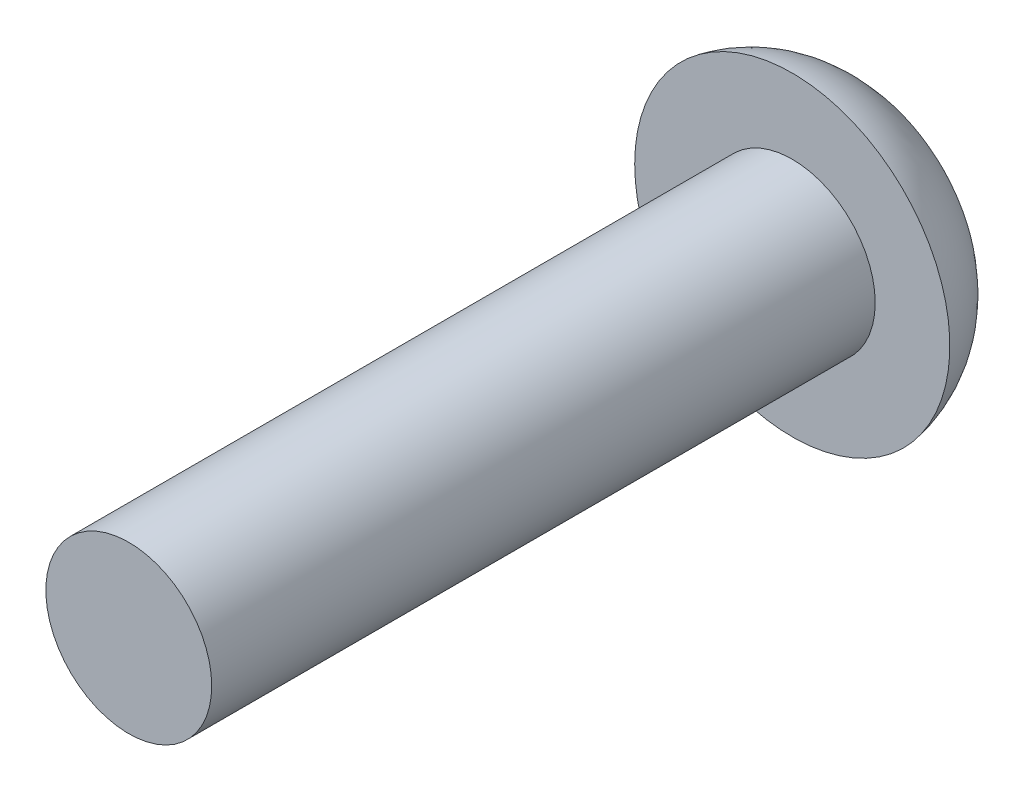
SolidWorks part; units mm, degrees
ref_plane "前视基准面" through (0, 0, 0) normal (0, 0, 1) x (1, 0, 0)
ref_plane "上视基准面" through (0, 0, 0) normal (0, 1, 0) x (1, 0, 0)
ref_plane "右视基准面" through (0, 0, 0) normal (1, 0, 0) x (0, 0, -1)
sketch "草图1" plane through (0, 0, 0) normal (0, 0, 1) x (1, 0, 0)
  circle A0 centre (0, 0) radius 1.5
extrude "凸台-拉伸1" add sketch "草图1" along normal blind 12
sketch "草图2" plane through (0, 0, 0) normal (0, 0, -1) x (-1, 0, 0)
  circle A0 centre (0, 0) radius 2.85
extrude "凸台-拉伸2" add sketch "草图2" along normal blind 1.65
fillet "圆角1" radius 2 1 edges at (-2.85, 0, -1.65)
